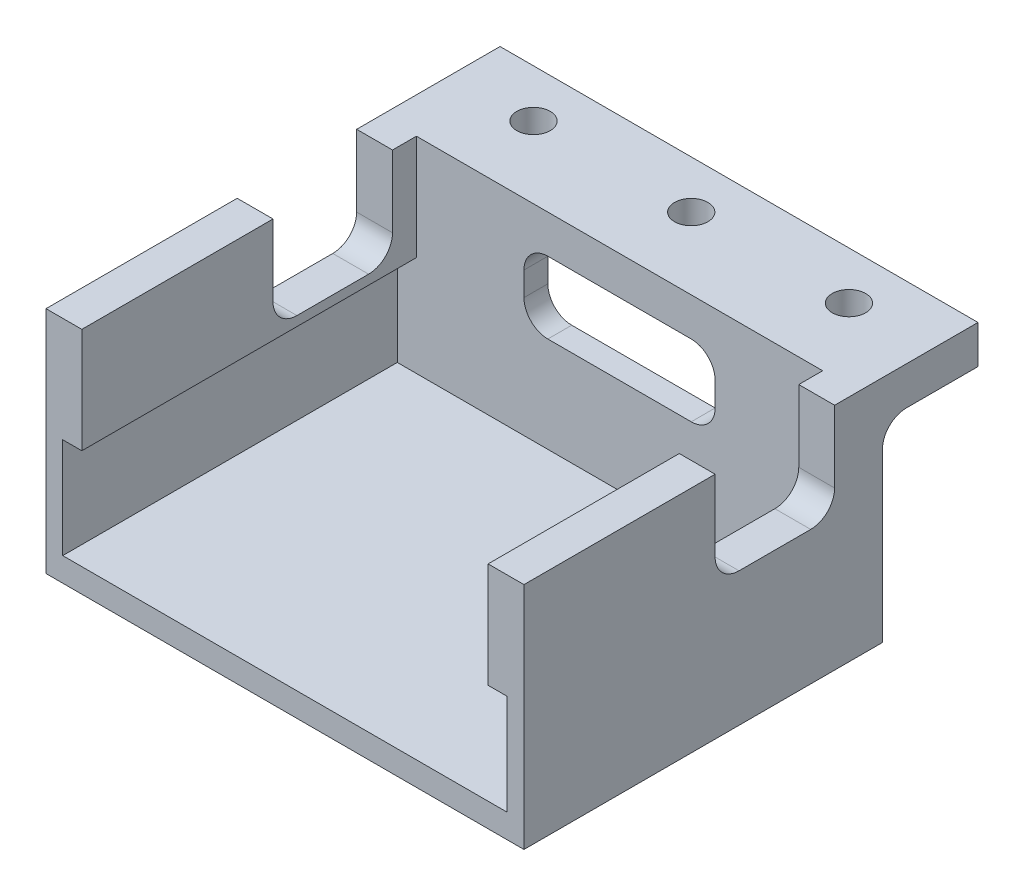
SolidWorks part; units mm, degrees
ref_plane "Ground" through (0, 0, 0) normal (0, 0, 1) x (1, 0, 0)
ref_plane "Right" through (0, 0, 0) normal (0, 1, 0) x (1, 0, 0)
ref_plane "Front" through (0, 0, 0) normal (1, 0, 0) x (0, 0, -1)
sketch "Sketch2" plane through (0, 0, 0) normal (0, 0, 1) x (1, 0, 0)
  line L1 (-25, -12) -> (25, -12)
  line L2 (-25, -12) -> (-25, 12)
  line L3 (-25, 12) -> (25, 12)
  line L4 (25, -12) -> (25, 12)
  line L7 (-23.25, -9.5) -> (23.25, -9.5)
  line L8 (-23.25, -9.5) -> (-23.25, 1)
  line L9 (-23.25, 1) -> (23.25, 1)
  line L10 (23.25, -9.5) -> (23.25, 1)
  line L11 (-21.25, 1) -> (21.25, 1)
  line L12 (-21.25, 1) -> (-21.25, 12)
  line L13 (21.25, 1) -> (21.25, 12)
  line L14 (-21.25, 12) -> (21.25, 12)
  point P0 (0, 0)
  point P6 (0, -4.25)
  point P11 (0, 12)
  point P13 (0, 6.5)
  point P17 (0, 12)
  dimension "D1" = 24
  dimension "D2" = 50
  dimension "D3" = 10.5
  dimension "D4" = 46.5
  dimension "D5" = 11
  dimension "D6" = 42.5
extrude "Boss-Extrude1" add sketch "Sketch2" along normal blind 47.5 contours L7 L10 L9 L8 | L1 L4 L3 L2 L10 L7 L8 L9 | L11 L12 L14 L13 region at (-24.4454, 0, 0) region at (0, -4.25, 0)
extrude "Cut-Extrude1" cut sketch "Sketch2<3>" against normal blind 35 from surface contours L7 L10 L9 L8 | L9 L13 L3 L12 region at (0, 6.5, 0) region at (0, -4.25, 0) starting at face at (0, 0, 47.5)
sketch "Sketch2<3>" plane through (0, 0, 0) normal (0, 0, 1) x (1, 0, 0) same geometry as "Sketch2"
sketch "Sketch3" plane through (0, -12, 0) normal (0, -1, 0) x (1, 0, 0)
  line L0 (-16.5, 5) -> (16.5, 5) construction
  line L2 (-25, 0) -> (25, 0)
  line L3 (-25, 0) -> (-25, 10)
  line L4 (-25, 0) -> (25, 0)
  line L5 (25, 0) -> (25, 47.5)
  line L6 (25, 47.5) -> (-25, 47.5)
  line L7 (-25, 47.5) -> (-25, 0)
  line L8 (-25, 0) -> (25, 0)
  line L9 (25, 0) -> (25, 47.5)
  line L10 (25, 47.5) -> (-25, 47.5)
  line L11 (-25, 47.5) -> (-25, 0)
  line L12 (-25, 10) -> (25, 10)
  line L13 (25, 0) -> (25, 10)
  line L14 (-25, 0) -> (25, 10) construction
  line L15 (-25, 10) -> (25, 0) construction
  circle A0 centre (-16.5, 5) radius 1.75
  circle A1 centre (16.5, 5) radius 1.75
  circle A2 centre (0, 5) radius 1.75
  point P8 (0, 5)
  line M13 (-25, 0) -> (25, 0)
  line M14 (25, 0) -> (25, 47.5)
  line M16 (-25, 47.5) -> (-25, 0)
  dimension "D2" = 3.5
  dimension "D3" = 33
  dimension "D4" = 5
  dimension "D1" = 0
extrude "Cut-Extrude2" cut sketch "Sketch3" against normal blind 20 contours L12 A2 A1 A0 M16 M13 M14 | A0 | A2 | A1 region at (-24.4901, -12, 5) region at (-16.5, -12, 5) region at (16.5, -12, 5) region at (0, -12, 5)
extrude "Cut-Extrude3" cut sketch "Sketch3<3>" against normal up to surface (24 mm away) contours A0 | A2 | A1 region at (-16.5, -12, 5) region at (16.5, -12, 5) region at (0, -12, 5) up to face at (0, 12, 26.875)
sketch "Sketch3<3>" plane through (0, -12, 0) normal (0, -1, 0) x (1, 0, 0) same geometry as "Sketch3"
sketch "Sketch4" plane through (25, 0, 0) normal (1, 0, 0) x (0, 0, -1)
  line L0 (-47.5, 12) -> (0, 12) construction
  line L1 (-27.5, 12) -> (-15, 12)
  line L2 (-27.5, 12) -> (-27.5, 2)
  line L3 (-27.5, 2) -> (-15, 2)
  line L4 (-15, 12) -> (-15, 2)
  line L5 (-47.5, -12) -> (-47.5, 12) construction
  dimension "D1" = 12.5
  dimension "D2" = 10
  dimension "D3" = 20
extrude "Cut-Extrude4" cut sketch "Sketch4" against normal up to surface (50 mm away) up to face at (-25, 2.6667, 19.1667)
sketch "Sketch5" plane through (0, 0, 12.5) normal (0, 0, 1) x (1, 0, 0)
  line L1 (-10, 0.5) -> (10, 0.5)
  line L2 (-10, 0.5) -> (-10, 8)
  line L3 (-10, 8) -> (10, 8)
  line L4 (10, 0.5) -> (10, 8)
  line L5 (-10, 0.5) -> (10, 8) construction
  line L6 (-10, 8) -> (10, 0.5) construction
  line L8 (-21.25, 1) -> (-23.25, 1)
  line L9 (-23.25, 1) -> (-23.25, -9.5)
  line L10 (-23.25, -9.5) -> (23.25, -9.5)
  line L11 (23.25, -9.5) -> (23.25, 1)
  line L12 (23.25, 1) -> (21.25, 1)
  line L13 (21.25, 1) -> (21.25, 12)
  line L14 (21.25, 12) -> (-21.25, 12)
  line L15 (-21.25, 12) -> (-21.25, 1)
  line L16 (-21.25, 1) -> (-23.25, 1)
  line L17 (-23.25, 1) -> (-23.25, -9.5)
  line L18 (-23.25, -9.5) -> (23.25, -9.5)
  line L19 (23.25, -9.5) -> (23.25, 1)
  line L20 (23.25, 1) -> (21.25, 1)
  line L21 (21.25, 1) -> (21.25, 12)
  line L22 (21.25, 12) -> (-21.25, 12)
  line L23 (-21.25, 12) -> (-21.25, 1)
  point P2 (0, 4.25)
  point P14 (0, 12)
  dimension "D2" = 4
  dimension "D3" = 7.5
  dimension "D4" = 20
  dimension "D1" = 0
extrude "Cut-Extrude5" cut sketch "Sketch5" against normal up to surface (2.5 mm away) contours L2 L1 L4 L3 up to face at (0, -2, 10)
fillet "Fillet1" radius 2.5 10 edges at (10, 8, 11.25) (-10, 8, 11.25) (10, 0.5, 11.25) (-10, 0.5, 11.25) (-23.125, 2, 27.5) (-23.125, 2, 15) (23.125, 2, 15) (23.125, 2, 27.5) (17.5, 8, 10) (-17.5, 8, 10)
